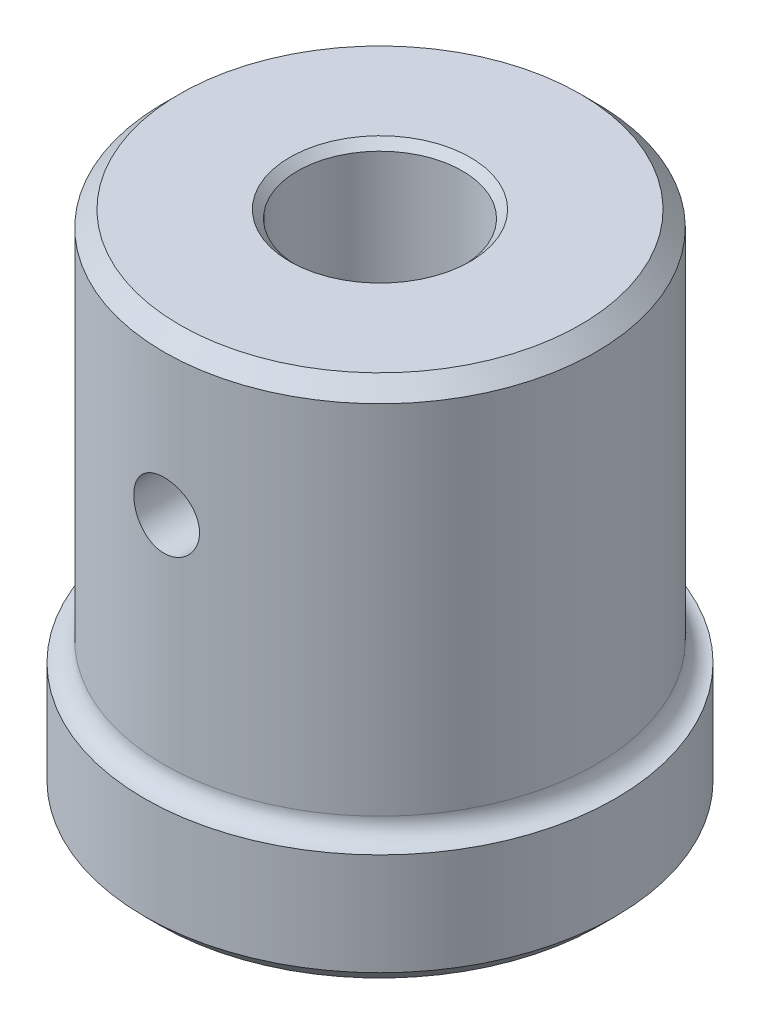
SolidWorks part; units mm, degrees
material "1.0060 (E335)"
ref_plane "Front Plane" through (0, 0, 0) normal (0, 0, 1) x (1, 0, 0)
ref_plane "Top Plane" through (0, 0, 0) normal (0, 1, 0) x (1, 0, 0)
ref_plane "Right Plane" through (0, 0, 0) normal (1, 0, 0) x (0, 0, -1)
sketch "Sketch1" plane through (0, 0, 0) normal (0, 1, 0) x (1, 0, 0)
  circle A0 centre (0, 0) radius 30
  dimension "D1" = 60
extrude "Boss-Extrude1" add sketch "Sketch1" along normal blind 15
sketch "Sketch2" plane through (0, 15, 0) normal (0, 1, 0) x (1, 0, 0)
  circle A0 centre (0, 0) radius 27.5
  dimension "D1" = 55
extrude "Boss-Extrude2" add sketch "Sketch2" along normal blind 50
sketch "Sketch3" plane through (0, 65, 0) normal (0, 1, 0) x (1, 0, 0)
  circle A0 centre (0, 0) radius 10.5
  dimension "D1" = 21
extrude "Cut-Extrude1" cut sketch "Sketch3" against normal blind 50
chamfer "Chamfer1" distance 2 angle 45 2 edges at (0, 65, 27.5) (0, 0, 30)
chamfer "Chamfer2" distance 1 angle 45 1 edges at (0, 65, 10.5)
fillet "Fillet1" radius 2.5 1 edges at (0, 15, 27.5)
sketch "Sketch4" plane through (0, 0, 0) normal (0, 0, 1) x (1, 0, 0)
  line L0 (0, -1000) -> (0, 49000) construction
  line L1 (0, 18) -> (-10.5, 18)
  line L2 (0, 15) -> (-10.5, 15)
  line L3 (0, 15) -> (0, 18)
  arc A0 (-10.5, 15) -> (-10.5, 18) centre (-10.5, 16.5) cw
  dimension "D1" = 3
  dimension "D2" = 21
  dimension "D3" = 15
revolve "Cut-Revolve1" cut sketch "Sketch4" angle 360 about L0
sketch "Sketch5" plane through (0, 0, 0) normal (0, 0, 1) x (1, 0, 0)
  line L0 (25.5, 65) -> (-25.5, 65) construction
  circle A0 centre (0, 45) radius 4.188
  dimension "D1" = 8.376
  dimension "D2" = 20
extrude "Cut-Extrude2" cut sketch "Sketch5" against normal through all both and the other way through all
